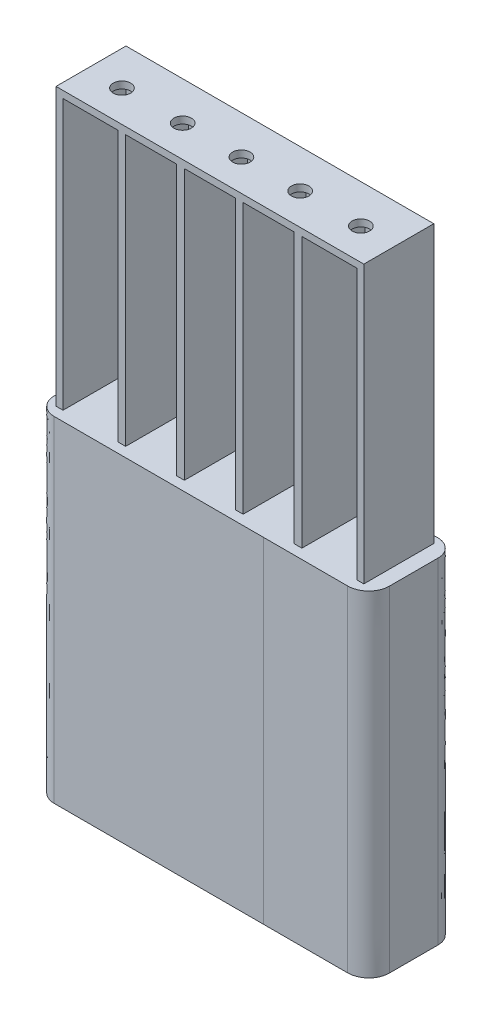
SolidWorks part; units mm, degrees
ref_plane "Front Plane" through (0, 0, 0) normal (0, 0, 1) x (1, 0, 0)
ref_plane "Top Plane" through (0, 0, 0) normal (0, 1, 0) x (1, 0, 0)
ref_plane "Right Plane" through (0, 0, 0) normal (1, 0, 0) x (0, 0, -1)
sketch "Sketch1" plane through (0, 0, 0) normal (0, 0, 1) x (1, 0, 0)
  line L1 (-44, -87.5) -> (44, -87.5)
  line L2 (-44, -87.5) -> (-44, 87.5)
  line L3 (-44, 87.5) -> (44, 87.5)
  line L4 (44, -87.5) -> (44, 87.5)
  line L5 (-44, -87.5) -> (44, 87.5) construction
  line L6 (-44, 87.5) -> (44, -87.5) construction
  point P0 (0, 0)
  dimension "D1" = 88
  dimension "D2" = 175
extrude "Boss-Extrude1" add sketch "Sketch1" along normal blind 2
sketch "Sketch2" plane through (0, 0, 2) normal (0, 0, 1) x (1, 0, 0)
  line L4 (44, -87.5) -> (44, 87.5)
  line L5 (44, 87.5) -> (-44, 87.5)
  line L6 (-44, 87.5) -> (-44, -87.5)
  line L7 (-44, -87.5) -> (44, -87.5)
  line L8 (44, -87.5) -> (44, 87.5)
  line L9 (44, 87.5) -> (-44, 87.5)
  line L10 (-44, 87.5) -> (-44, -87.5)
  line L11 (-44, -87.5) -> (44, -87.5)
  dimension "D1" = 0
extrude "Extrude-Thin1" add sketch "Sketch2" along normal blind 18 thin thin type one direction reverse wall 2
sketch "Sketch3" plane through (0, 0, 2) normal (0, 0, 1) x (1, 0, 0)
  line L0 (-25.2, 85.5) -> (-25.2, -85.5)
  line L1 (42, 85.5) -> (-42, 85.5) construction
  line L2 (-42, -85.5) -> (42, -85.5) construction
  line L3 (-8.4, 85.5) -> (-8.4, -85.5)
  line L4 (42, 85.5) -> (-42, 85.5) construction
  line L5 (25.2, 85.5) -> (25.2, -85.5)
  line L6 (8.4, 85.5) -> (8.4, -85.5)
  line L7 (-42, -85.5) -> (42, -85.5) construction
  line L8 (-42, 85.5) -> (-42, -85.5) construction
  line L9 (42, -85.5) -> (42, 85.5) construction
  dimension "D1" = 16.8
  dimension "D2" = 16.8
  dimension "D3" = 16.8
  dimension "D4" = 16.8
  dimension "D5" = 16.8
extrude "Extrude-Thin2" add sketch "Sketch3" along normal blind 18 thin thin type mid plane wall 2.2
sketch "Sketch4" plane through (0, 87.5, 0) normal (0, 1, 0) x (1, 0, 0)
  line L0 (26.3, -20) -> (26.3, -2) construction
  line L1 (26.3, -2) -> (42, -2) construction
  line L2 (42, -2) -> (42, -20) construction
  line L3 (42, -20) -> (26.3, -20) construction
  line L4 (9.5, -20) -> (9.5, -2) construction
  line L5 (9.5, -2) -> (24.1, -2) construction
  line L6 (24.1, -2) -> (24.1, -20) construction
  line L7 (24.1, -20) -> (9.5, -20) construction
  line L8 (-7.3, -2) -> (7.3, -2) construction
  line L9 (7.3, -2) -> (7.3, -20) construction
  line L10 (7.3, -20) -> (-7.3, -20) construction
  line L11 (-7.3, -20) -> (-7.3, -2) construction
  line L12 (-24.1, -2) -> (-9.5, -2) construction
  line L13 (-9.5, -2) -> (-9.5, -20) construction
  line L14 (-9.5, -20) -> (-24.1, -20) construction
  line L15 (-24.1, -20) -> (-24.1, -2) construction
  line L16 (-42, -2) -> (-26.3, -2) construction
  line L17 (-26.3, -2) -> (-26.3, -20) construction
  line L18 (-26.3, -20) -> (-42, -20) construction
  line L19 (-42, -20) -> (-42, -2) construction
  line L20 (26.3, -20) -> (26.3, -2) construction
  line L21 (26.3, -2) -> (42, -2) construction
  line L22 (42, -2) -> (42, -20) construction
  line L23 (42, -20) -> (26.3, -20) construction
  line L24 (9.5, -20) -> (9.5, -2) construction
  line L25 (9.5, -2) -> (24.1, -2) construction
  line L26 (24.1, -2) -> (24.1, -20) construction
  line L27 (24.1, -20) -> (9.5, -20) construction
  line L28 (-7.3, -2) -> (7.3, -2) construction
  line L29 (7.3, -2) -> (7.3, -20) construction
  line L30 (7.3, -20) -> (-7.3, -20) construction
  line L31 (-7.3, -20) -> (-7.3, -2) construction
  line L32 (-24.1, -2) -> (-9.5, -2) construction
  line L33 (-9.5, -2) -> (-9.5, -20) construction
  line L34 (-9.5, -20) -> (-24.1, -20) construction
  line L35 (-24.1, -20) -> (-24.1, -2) construction
  line L36 (-42, -2) -> (-26.3, -2) construction
  line L37 (-26.3, -2) -> (-26.3, -20) construction
  line L38 (-26.3, -20) -> (-42, -20) construction
  line L39 (-42, -20) -> (-42, -2) construction
  line L40 (42, -11) -> (-42, -11) construction
  line L41 (-16.8, -20) -> (-16.8, -2) construction
  line L42 (-34.15, -20) -> (-34.15, -2) construction
  line L43 (0, -20) -> (0, -2) construction
  line L44 (16.8, -20) -> (16.8, -2) construction
  line L45 (34.15, -20) -> (34.15, -2) construction
  point P26 (34.15, -11)
  point P28 (16.8, -11)
  point P30 (0, -11)
  point P31 (-16.8, -11)
  point P34 (-34.15, -11)
hole_wizard "Ø5.0mm Dowel Hole3" positions "Sketch5" profile "Sketch6" hole size "Ø5.0" standard "BSI" end condition up to next
sketch "Sketch5" plane through (0, 87.5, 0) normal (0, 1, 0) x (1, 0, 0)
  line L0 (-34.15, -20) -> (-34.15, -2) construction
  line L1 (-16.8, -20) -> (-16.8, -2) construction
  point P0 (-34.15, -11)
  point P4 (-16.8, -11)
  point P8 (0, -11)
  point P11 (16.8, -11)
  point P14 (34.15, -11)
sketch "Sketch6" plane through (-34.15, 87.5, 11) normal (1, 0, 0) x (0, 0, 1)
  line L0 (0, 0) -> (0, 2)
  line L1 (0, 2) -> (2.5, 2)
  line L2 (2.5, 2) -> (2.5, 0)
  line L5 (2.5, 0) -> (0, 0)
  line L11 (0, -6.35) -> (0, 107.95) construction
  dimension "Thru Hole Dia." = 5
  dimension "Thru Hole Depth" = 2
sketch "Sketch7" plane through (0, -87.5, 0) normal (0, -1, 0) x (1, 0, 0)
  line L5 (-41.7947, -2) -> (43.1333, -2)
  line L6 (48.2045, 2.9357) -> (48.2045, 16.9113)
  line L7 (42.125, 22.8183) -> (18.1019, 22.8081)
  line L8 (18.1019, 22.8081) -> (-41.7556, 22.7981)
  line L9 (-46.7955, 17.7993) -> (-46.7955, 2.97)
  line L10 (-41.7947, -2) -> (43.1333, -2)
  line L11 (48.2045, 2.9357) -> (48.2045, 16.9113)
  line L12 (42.125, 22.8183) -> (18.1019, 22.8081)
  line L13 (18.1019, 22.8081) -> (-41.7556, 22.7981)
  line L14 (-46.7955, 17.7993) -> (-46.7955, 2.97)
  spline S4 degree 3 poles (-750.9272, 3917.0514) (-135.4802, 531.1061) (0.6079, -10.1247) (44.4297, -1.8483) (44.748, -1.7568) (45.359, -1.5153) (45.6493, -1.3671) (46.1994, -1.0159) (46.4616, -0.8102) (46.9336, -0.3574) (47.1455, -0.1099) (47.4262, 0.2936) (47.514, 0.4343) (47.6737, 0.7219) (47.7457, 0.8688) (47.9389, 1.3182) (48.0374, 1.6296) (58.0724, 50.2404) (-675.8515, 189.6655) (-2010.8516, -3341.219) knots -16.851056 -16.851056 -16.851056 -16.851056 0.125 0.125 0.25 0.25 0.375 0.375 0.5 0.5 0.625 0.625 0.6875 0.6875 0.75 0.75 0.875 0.875 19.519675 19.519675 19.519675 19.519675 only from (43.1333, -2) to (48.2045, 2.9357)
  spline S5 degree 3 poles (-3867.134, -793.8696) (-527.4108, -178.0473) (57.798, -29.5205) (48.0477, 18.2712) (47.9989, 18.461) (47.8815, 18.8372) (47.8126, 19.0236) (47.5808, 19.5649) (47.3916, 19.9066) (47.0561, 20.3904) (46.9348, 20.5478) (46.6788, 20.8475) (46.5441, 20.9899) (46.1207, 21.3956) (45.8129, 21.6376) (45.1451, 22.0633) (44.7957, 22.2403) (44.0682, 22.5266) (43.6865, 22.6364) (-29.4495, 36.3869) (-257.3123, -1235.7243) (-654.776, -3913.7129) knots -15.414657 -15.414657 -15.414657 -15.414657 0.125 0.125 0.1875 0.1875 0.25 0.25 0.375 0.375 0.4375 0.4375 0.5 0.5 0.625 0.625 0.75 0.75 0.875 0.875 24.367427 24.367427 24.367427 24.367427 only from (48.2045, 16.9113) to (42.125, 22.8183)
  spline S6 degree 3 poles (747.8118, -3897.2269) (119.209, -442.763) (-2.6586, 30.5638) (-42.894, 22.6717) (-43.053, 22.6324) (-43.3684, 22.5381) (-43.5253, 22.4827) (-43.982, 22.2959) (-44.271, 22.1434) (-44.8182, 21.7829) (-45.0779, 21.5726) (-45.5439, 21.1126) (-45.7531, 20.8616) (-46.0304, 20.4526) (-46.1168, 20.3104) (-46.2734, 20.0213) (-46.3441, 19.8738) (-46.534, 19.422) (-46.6314, 19.1076) (-58.2179, -38.155) (938.6019, -203.9534) (3906.2126, -582.5183) knots -15.49454 -15.49454 -15.49454 -15.49454 0.125 0.125 0.1875 0.1875 0.25 0.25 0.375 0.375 0.5 0.5 0.625 0.625 0.6875 0.6875 0.75 0.75 0.875 0.875 22.814887 22.814887 22.814887 22.814887 only from (-41.7556, 22.7981) to (-46.7955, 17.7993)
  spline S7 degree 3 poles (3872.9223, 793.5434) (437.8635, 167.8572) (-54.7504, 42.3725) (-46.6679, 1.8393) (-46.6283, 1.6814) (-46.5331, 1.3683) (-46.4771, 1.2127) (-46.2887, 0.7605) (-46.1349, 0.4746) (-45.7714, -0.0662) (-45.5599, -0.3219) (-45.0982, -0.7797) (-44.8463, -0.985) (-44.2993, -1.3471) (-44.009, -1.5004) (-43.4082, -1.7468) (-43.0937, -1.8415) (16.5277, -13.5762) (197.1828, 1047.1688) (585.9157, 3946.6907) knots -15.721199 -15.721199 -15.721199 -15.721199 0.125 0.125 0.1875 0.1875 0.25 0.25 0.375 0.375 0.5 0.5 0.625 0.625 0.75 0.75 0.875 0.875 23.890728 23.890728 23.890728 23.890728 only from (-46.7955, 2.97) to (-41.7947, -2)
  spline S8 degree 3 poles (43.1333, -2) (43.4638, -2) (43.7891, -1.9693) (44.4297, -1.8483) (44.748, -1.7568) (45.359, -1.5153) (45.6493, -1.3671) (46.1994, -1.0159) (46.4616, -0.8102) (46.9336, -0.3574) (47.1455, -0.1099) (47.4262, 0.2936) (47.514, 0.4343) (47.6737, 0.7219) (47.7457, 0.8688) (47.9389, 1.3182) (48.0374, 1.6296) (48.1711, 2.2771) (48.2045, 2.6049) (48.2045, 2.9357) knots 0 0 0 0 0.125 0.125 0.25 0.25 0.375 0.375 0.5 0.5 0.625 0.625 0.6875 0.6875 0.75 0.75 0.875 0.875 1 1 1 1
  spline S9 degree 3 poles (48.2045, 16.9113) (48.2045, 17.3074) (48.1648, 17.6968) (48.0477, 18.2712) (47.9989, 18.461) (47.8815, 18.8372) (47.8126, 19.0236) (47.5808, 19.5649) (47.3916, 19.9066) (47.0561, 20.3904) (46.9348, 20.5478) (46.6788, 20.8475) (46.5441, 20.9899) (46.1207, 21.3956) (45.8129, 21.6376) (45.1451, 22.0633) (44.7957, 22.2403) (44.0682, 22.5266) (43.6865, 22.6364) (42.9123, 22.7819) (42.5209, 22.8183) (42.125, 22.8183) knots 0 0 0 0 0.125 0.125 0.1875 0.1875 0.25 0.25 0.375 0.375 0.4375 0.4375 0.5 0.5 0.625 0.625 0.75 0.75 0.875 0.875 1 1 1 1
  spline S10 degree 3 poles (-41.7556, 22.7981) (-42.087, 22.7981) (-42.4129, 22.766) (-42.894, 22.6717) (-43.053, 22.6324) (-43.3684, 22.5381) (-43.5253, 22.4827) (-43.982, 22.2959) (-44.271, 22.1434) (-44.8182, 21.7829) (-45.0779, 21.5726) (-45.5439, 21.1126) (-45.7531, 20.8616) (-46.0304, 20.4526) (-46.1168, 20.3104) (-46.2734, 20.0213) (-46.3441, 19.8738) (-46.534, 19.422) (-46.6314, 19.1076) (-46.7626, 18.4588) (-46.7955, 18.1308) (-46.7955, 17.7993) knots 0 0 0 0 0.125 0.125 0.1875 0.1875 0.25 0.25 0.375 0.375 0.5 0.5 0.625 0.625 0.6875 0.6875 0.75 0.75 0.875 0.875 1 1 1 1
  spline S11 degree 3 poles (-46.7955, 2.97) (-46.7955, 2.6408) (-46.7632, 2.317) (-46.6679, 1.8393) (-46.6283, 1.6814) (-46.5331, 1.3683) (-46.4771, 1.2127) (-46.2887, 0.7605) (-46.1349, 0.4746) (-45.7714, -0.0662) (-45.5599, -0.3219) (-45.0982, -0.7797) (-44.8463, -0.985) (-44.2993, -1.3471) (-44.009, -1.5004) (-43.4082, -1.7468) (-43.0937, -1.8415) (-42.4496, -1.9682) (-42.1239, -2) (-41.7947, -2) knots 0 0 0 0 0.125 0.125 0.1875 0.1875 0.25 0.25 0.375 0.375 0.5 0.5 0.625 0.625 0.75 0.75 0.875 0.875 1 1 1 1
  dimension "D1" = 0
extrude "Boss-Extrude2" add sketch "Sketch7" against normal up to surface (95.8124 mm away)
